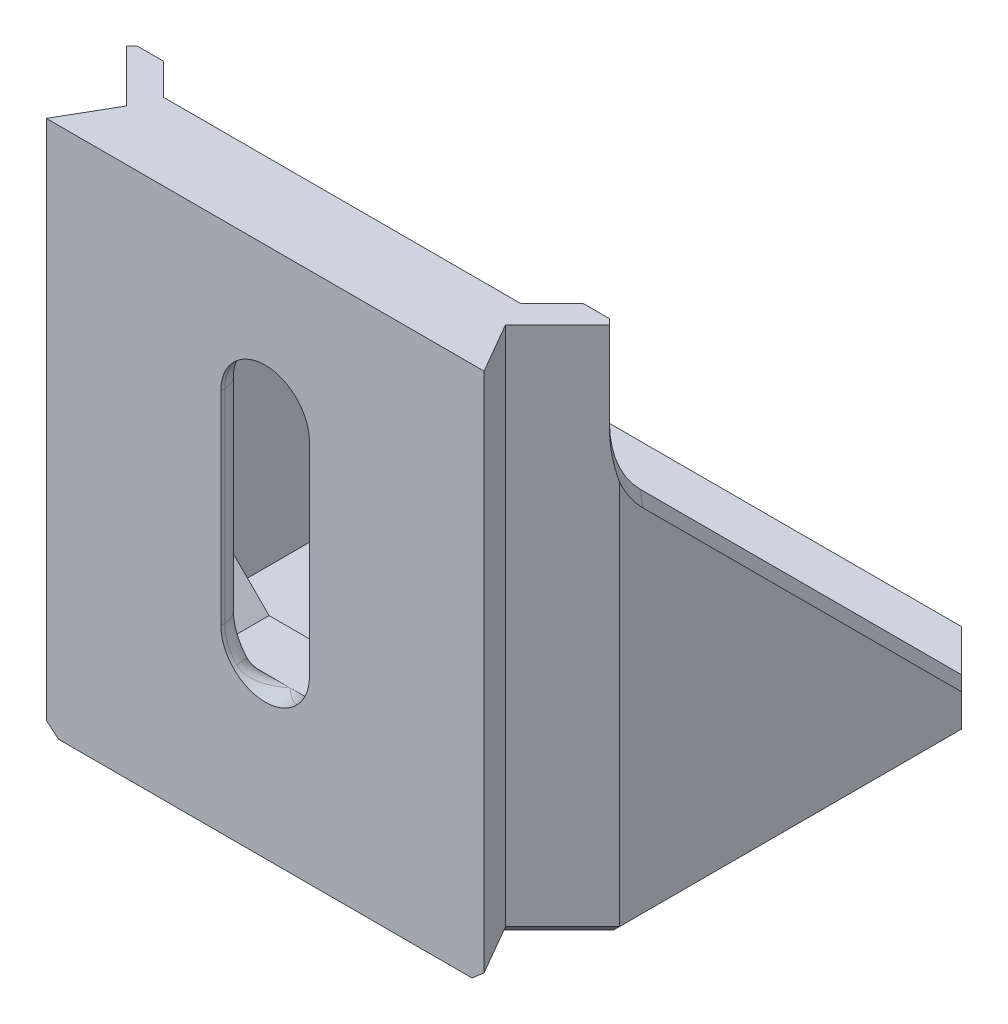
SolidWorks part; units mm, degrees
ref_plane "Front Plane" through (0, 0, 0) normal (0, 0, 1) x (1, 0, 0)
ref_plane "Top Plane" through (0, 0, 0) normal (0, 1, 0) x (1, 0, 0)
ref_plane "Right Plane" through (0, 0, 0) normal (1, 0, 0) x (0, 0, -1)
sketch "Sketch1" plane through (0, 0, 0) normal (0, 1, 0) x (1, 0, 0)
  line L0 (-21.15, 17.15) -> (-17.15, 21.15)
  line L1 (-17.15, -21.15) -> (17.15, -21.15)
  line L2 (-21.15, -17.15) -> (-21.15, 17.15)
  line L3 (-17.15, 21.15) -> (17.15, 21.15)
  line L4 (21.15, -17.15) -> (21.15, 17.15)
  line L5 (-21.15, -21.15) -> (21.15, 21.15) construction
  line L6 (-21.15, 21.15) -> (21.15, -21.15) construction
  line L7 (-21.15, -17.15) -> (-17.15, -21.15)
  line L8 (17.15, -21.15) -> (21.15, -17.15)
  line L9 (17.15, 21.15) -> (21.15, 17.15)
  circle A0 centre (-15.5, 15.5) radius 1.5
  circle A1 centre (15.5, 15.5) radius 1.5
  circle A2 centre (15.5, -15.5) radius 1.5
  circle A3 centre (-15.5, -15.5) radius 1.5
  circle A4 centre (0, 0) radius 11.5
  point P0 (0, 0)
  dimension "D3" = 3
  dimension "D4" = 3
  dimension "D9" = 3
  dimension "D10" = 3
  dimension "D12" = 23
  dimension "D1" = 42.3
  dimension "D2" = 42.3
  dimension "D11" = 31
extrude "Boss-Extrude1" add sketch "Sketch1" along normal blind 3
sketch "Sketch5" plane through (0, 0, 0) normal (0, 1, 0) x (1, 0, 0)
  line L16 (-23.65, 18.1855) -> (-23.65, -18.1855)
  line L17 (-23.65, -18.1855) -> (-18.1855, -23.65)
  line L18 (-18.1855, -23.65) -> (18.1855, -23.65)
  line L19 (18.1855, -23.65) -> (23.65, -18.1855)
  line L20 (23.65, -18.1855) -> (23.65, 18.1855)
  line L21 (23.65, 18.1855) -> (18.1855, 23.65)
  line L22 (18.1855, 23.65) -> (-18.1855, 23.65)
  line L23 (-18.1855, 23.65) -> (-23.65, 18.1855)
  line L24 (-23.65, 14.65) -> (-23.65, -18.1855)
  line L25 (-23.65, -18.1855) -> (-18.1855, -23.65)
  line L26 (-18.1855, -23.65) -> (18.1855, -23.65)
  line L27 (18.1855, -23.65) -> (23.65, -18.1855)
  line L28 (23.65, -18.1855) -> (23.65, 14.65)
  line L29 (23.65, 18.1855) -> (18.1855, 23.65) construction
  line L30 (18.1855, 23.65) -> (-18.1855, 23.65) construction
  line L31 (-18.1855, 23.65) -> (-23.65, 18.1855) construction
  line L32 (-21.15, 17.15) -> (-23.65, 14.65)
  line L33 (21.15, 17.15) -> (23.65, 14.65)
  line L34 (-23.65, 18.1855) -> (-23.65, 14.65) construction
  line L35 (23.65, 14.65) -> (23.65, 18.1855) construction
  line L40 (-21.15, 17.15) -> (-21.15, -17.15)
  line L41 (-21.15, -17.15) -> (-17.15, -21.15)
  line L42 (-17.15, -21.15) -> (17.15, -21.15)
  line L43 (17.15, -21.15) -> (21.15, -17.15)
  line L44 (21.15, -17.15) -> (21.15, 17.15)
  line L45 (21.15, 17.15) -> (17.15, 21.15)
  line L46 (17.15, 21.15) -> (-17.15, 21.15)
  line L47 (-17.15, 21.15) -> (-21.15, 17.15)
  line L48 (-21.15, 17.15) -> (-21.15, -17.15)
  line L49 (-21.15, -17.15) -> (-17.15, -21.15)
  line L50 (-17.15, -21.15) -> (17.15, -21.15)
  line L51 (17.15, -21.15) -> (21.15, -17.15)
  line L52 (21.15, -17.15) -> (21.15, 17.15)
  line L53 (21.15, 17.15) -> (17.15, 21.15) construction
  line L54 (17.15, 21.15) -> (-17.15, 21.15) construction
  line L55 (-17.15, 21.15) -> (-21.15, 17.15) construction
  dimension "D1" = 2.5
  dimension "D2" = 0
extrude "Boss-Extrude2" add sketch "Sketch5" along normal blind 51
sketch "Sketch6" plane through (0, 0, 0) normal (1, 0, 0) x (0, 0, -1)
  line L0 (17.15, 3) -> (-18.15, 38.3)
  line L1 (-18.15, 38.3) -> (-18.15, 51)
  line L2 (-23.65, 51) -> (-18.1855, 51) construction
  line L3 (-18.15, 51) -> (17.15, 51)
  line L4 (17.15, 51) -> (17.15, 3)
  line L5 (-23.65, 51) -> (-23.65, 0) construction
  dimension "D1" = 5.5
  dimension "D2" = 45
extrude "Cut-Extrude1" cut sketch "Sketch6" against normal through all both and the other way through all
fillet "Fillet1" radius 10 2 edges at (-21.9, 38.3, 18.15) (21.9, 38.3, 18.15)
sketch "Sketch9" plane through (0, 0, 0) normal (0, 1, 0) x (1, 0, 0)
  line L0 (-18.1855, -23.65) -> (-21, -28.5248)
  line L1 (-21, -28.5248) -> (21, -28.5248)
  line L2 (21, -28.5248) -> (18.1855, -23.65)
  line L3 (18.1855, -23.65) -> (-18.1855, -23.65)
  dimension "D1" = 60
  dimension "D2" = 60
  dimension "D3" = 42
extrude "Boss-Extrude3" add sketch "Sketch9" along normal blind 51
sketch "Sketch13" plane through (0, 51, 0) normal (0, 1, 0) x (1, 0, 0)
  line L0 (-17.15, -21.15) -> (17.15, -21.15) construction
  line L1 (-12, -21.15) -> (12, -21.15)
  line L2 (-12, -21.15) -> (-12, -26.15)
  line L3 (-12, -26.15) -> (12, -26.15)
  line L4 (12, -21.15) -> (12, -26.15)
  point P6 (0, -21.15)
  dimension "D1" = 24
  dimension "D2" = 5
extrude "Cut-Extrude3" cut sketch "Sketch13" against normal offset from surface (28 mm away) 10 from offset 10 up to face at (0, 3, 0) offset against normal yes
sketch "Sketch14" plane through (0, 0, 26.15) normal (0, 0, -1) x (-1, 0, 0)
  line L0 (0, 17.25) -> (0, 36.75) construction
  line L1 (-4.25, 17.25) -> (-4.25, 36.75)
  line L2 (4.25, 17.25) -> (4.25, 36.75)
  line L3 (12, 41) -> (-12, 41) construction
  line L4 (12, 13) -> (-12, 13) construction
  arc A0 (-4.25, 17.25) -> (4.25, 17.25) centre (0, 17.25) ccw
  arc A1 (4.25, 36.75) -> (-4.25, 36.75) centre (0, 36.75) ccw
  point P2 (0, 27)
  dimension "D1" = 8.5
extrude "Cut-Extrude4" cut sketch "Sketch14" against normal blind 10
fillet "Fillet3" radius 2 6 edges at (3.0052, 39.7552, 26.15) (-3.0052, 39.7552, 26.15) (-4.25, 27, 26.15) (-3.0052, 14.2448, 26.15) (3.0052, 14.2448, 26.15) (4.25, 27, 26.15)
chamfer "Chamfer1" distance 5 angle 45 2 edges at (-12, 13, 23.65) (12, 13, 23.65)
chamfer "Chamfer2" distance 1 angle 45 1 edges at (0, 0, 11.5)
chamfer "Chamfer3" distance 1 angle 45 9 edges at (19.5928, 0, 26.0874) (-19.5928, 0, 26.0874) (-20.9178, 0, 20.9178) (20.9178, 0, 20.9178) (-23.65, 0, 1.7678) (23.65, 0, 1.7678) (20.4, 0, -17.9) (-20.4, 0, -17.9) (0, 0, -21.15)
chamfer "Chamfer4" distance 1 angle 45 6 edges at (-23.65, 46.7211, 18.15) (-23.65, 38.6153, 17.3888) (-23.65, 20.4355, 0.2855) (23.65, 46.7211, 18.15) (23.65, 38.6153, 17.3888) (23.65, 20.4355, 0.2855)
